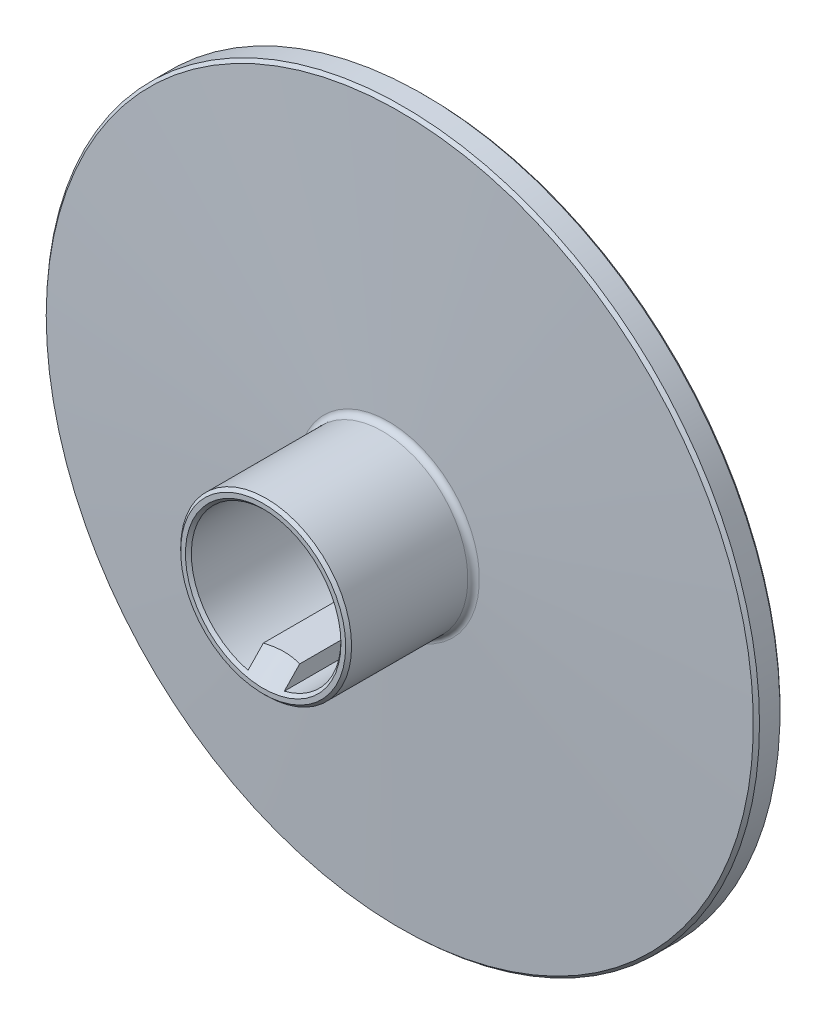
SolidWorks part; units mm, degrees
ref_plane "Front Plane" through (0, 0, 0) normal (0, 0, 1) x (1, 0, 0)
ref_plane "Top Plane" through (0, 0, 0) normal (0, 1, 0) x (1, 0, 0)
ref_plane "Right Plane" through (0, 0, 0) normal (1, 0, 0) x (0, 0, -1)
sketch "Sketch1" plane through (0, 0, 0) normal (0, 0, 1) x (1, 0, 0)
  circle A0 centre (0, 0) radius 22.25
  dimension "D1" = 44.5
extrude "Boss-Extrude1" add sketch "Sketch1" along normal blind 6
sketch "Sketch2" plane through (0, 0, 0) normal (0, 1, 0) x (1, 0, 0)
  line L0 (-14.5, -12.5084) -> (-14.5, -33.7)
  line L1 (-14.5, -33.7) -> (0, -33.7)
  line L2 (0, -33.7) -> (0, -47.0021) construction
  line L3 (-14.5, -12.5084) -> (-60.5, -10.5)
  line L4 (-60.5, -10.5) -> (-60.5, -6)
  line L5 (-60.5, -6) -> (0, -6)
  line L6 (-22.25, -6) -> (22.25, -6) construction
  line L7 (0, -6) -> (0, -33.7)
  line L8 (22.25, 0) -> (-22.25, 0) construction
  dimension "D1" = 29
  dimension "D2" = 121
  dimension "D3" = 33.7
  dimension "D4" = 2.5
  dimension "D5" = 4.5
revolve "Revolve1" add sketch "Sketch2" angle 360 about L2
fillet "Fillet1" radius 1 1 edges at (22.25, 0, 6)
sketch "Sketch3" plane through (0, 0, 33.7) normal (0, 0, 1) x (1, 0, 0)
  circle A0 centre (0, 0) radius 12.695
  dimension "D1" = 25.39
extrude "Cut-Extrude1" cut sketch "Sketch3" against normal through all
chamfer "Chamfer1" distance 0.5 angle 45 4 edges at (-60.5, 0, 6) (-60.5, 0, 10.5) (-14.5, 0, 33.7) (22.25, 0, 0) first distance on face at (-60.5, 0, 10.5) first distance on face at (-14.5, 0, 12.5084) first distance on face at (12.695, 0, 33.7) first distance on face at (12.695, 0, 0)
sketch "Sketch4" plane through (0, 0, 33.7) normal (0, 0, 1) x (1, 0, 0)
  line L0 (0, 0) -> (0, 5.8142) construction
  line L1 (-3.075, -12.317) -> (-3.075, -9.61)
  line L2 (3.075, -12.317) -> (3.075, -9.61)
  line L3 (-3.075, -9.61) -> (3.075, -9.61)
  circle A0 centre (0, 0) radius 12.695 construction
  circle A11 centre (0, 0) radius 14.5 construction
  arc A12 (-3.075, -12.317) -> (3.075, -12.317) centre (0, 0) ccw
  dimension "D1" = 6.15
  dimension "D2" = 4.89
  dimension "D3" = 22.305
extrude "Boss-Extrude2" add sketch "Sketch4" against normal blind 20
sketch "Sketch5" plane through (0, 0, 0) normal (0, 1, 0) x (1, 0, 0)
  line L0 (-12.695, -33.7) -> (-12.695, -33.2)
  line L1 (-12.695, 0) -> (-12.695, -33.7) construction
  line L2 (-12.695, -33.2) -> (-13.195, -33.7)
  line L3 (-13.195, -33.7) -> (-12.695, -33.7)
  line L4 (-12.695, -33.2) -> (-9.195, -29.7)
  line L5 (-9.195, -29.7) -> (-9.195, -33.7)
  line L6 (-14, -33.7) -> (14, -33.7) construction
  line L7 (-9.195, -33.7) -> (-12.695, -33.7)
  line L8 (0, 0) -> (0, 15.87) construction
  dimension "D1" = 0.5
  dimension "D2" = 0.5
  dimension "D3" = 4
revolve "Cut-Revolve1" cut sketch "Sketch5" angle 360 about L8 region at (-12.8617, 0, 33.5333) region at (-10.4913, 0, 32.3481)
chamfer "Chamfer2" distance 3.5 angle 45 1 edges at (0, -9.61, 13.7)
fillet "Fillet2" radius 1 1 edges at (-14.5, 0, 12.5084)
ref_plane "Plane1" through (0, 0, 13.4657) normal (0, 0, 1) x (1, 0, 0)
